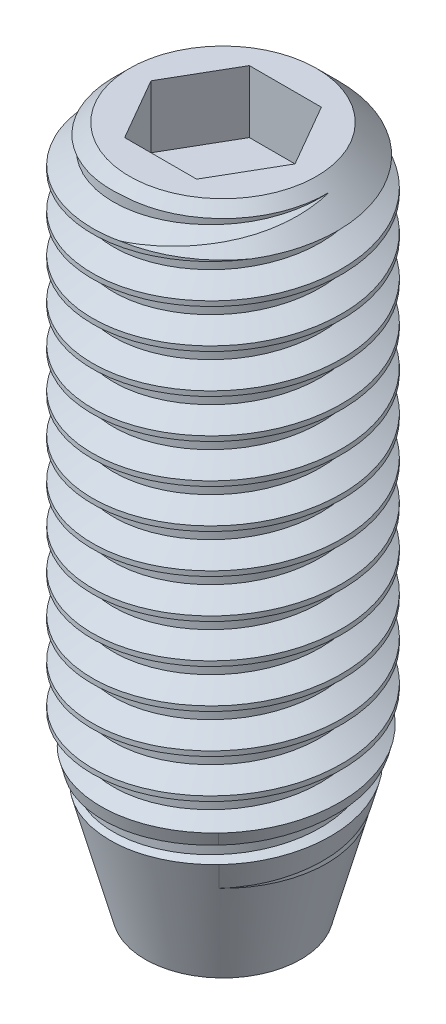
SolidWorks part; units mm, degrees
material "AISI 1020"
ref_plane "Front Plane" through (0, 0, 0) normal (0, 0, 1) x (1, 0, 0)
ref_plane "Top Plane" through (0, 0, 0) normal (0, 1, 0) x (1, 0, 0)
ref_plane "Right Plane" through (0, 0, 0) normal (1, 0, 0) x (0, 0, -1)
sketch "Sketch4" plane through (0, 0, 0) normal (0, 0, 1) x (1, 0, 0)
  line L0 (0, 0) -> (0, 22) construction
  line L1 (0, 0) -> (2.5, 0)
  line L2 (2.5, 0) -> (4, 5.5981)
  line L3 (4, 5.5981) -> (4, 21)
  line L4 (3, 22) -> (0, 22)
  line L5 (4, 21) -> (3, 22)
  line L6 (0, 0) -> (0, 22)
  point P6 (4, 22)
  dimension "D1" = 5
  dimension "D2" = 8
  dimension "D3" = 75
  dimension "D4" = 22
revolve "Revolve1" add sketch "Sketch4" angle 360 about L0
sketch "Sketch5" plane through (0, 22, 0) normal (0, 1, 0) x (1, 0, 0)
  line L1 (2.3094, 0) -> (1.1547, 2)
  line L2 (1.1547, 2) -> (-1.1547, 2)
  line L3 (-1.1547, 2) -> (-2.3094, 0)
  line L4 (-2.3094, 0) -> (-1.1547, -2)
  line L5 (-1.1547, -2) -> (1.1547, -2)
  line L6 (1.1547, -2) -> (2.3094, 0)
  circle A0 centre (0, 0) radius 2 construction
  circle A1 centre (0, 0) radius 3 construction
  dimension "D1" = 1
extrude "Cut-Extrude1" cut sketch "Sketch5" against normal blind 2
thread "Thread1" pitch 1.25 method cut profile "Thread Profile1" start angle 0, offset 2, length 0, pitch 1.25, diameter 8
ref_plane "Plane2" through (-4, 23, 0) normal (0, 0, 1) x (-1, 0, 0)
sketch "Thread Profile1" plane through (-4, 23, 0) normal (0, 0, 1) x (-1, 0, 0)
  line L0 (0, 0) -> (0, 1.25) construction
  line L11 (0, 0) -> (0, 1.0937)
  line L12 (0, 1.0937) -> (-0.6766, 0.7031)
  line L13 (-0.6766, 0.7031) -> (-0.6766, 0.3906)
  line L15 (-0.6766, 0.3906) -> (0, 0)
  line L17 (-0.6766, 0.5469) -> (0, 0.5469) construction
  point P2 (0, 0)
  dimension "Pitch" = 1.25
  dimension "Profile_Angle" = 60
  dimension "Profile_Land" = 0.3125
  dimension "Profile_Height" = 0.6766
